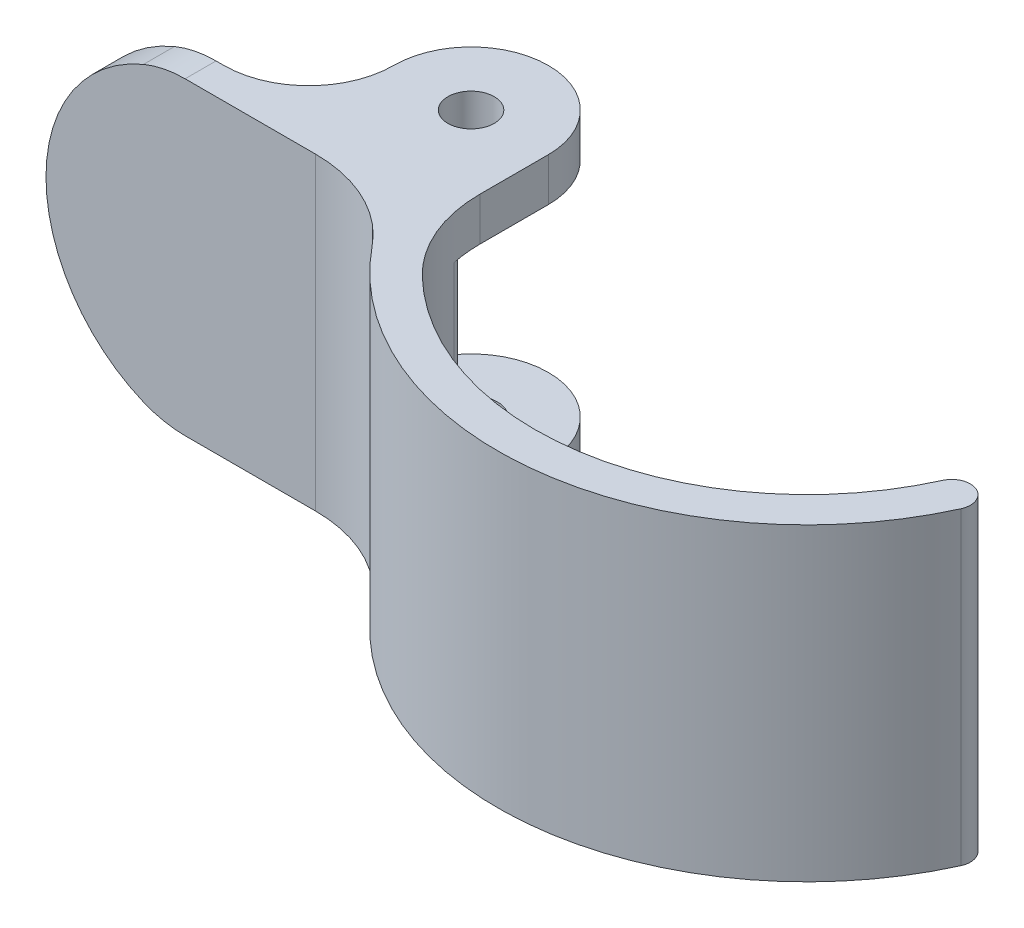
SolidWorks part; units mm, degrees
ref_plane "Front Plane" through (0, 0, 0) normal (0, 0, 1) x (1, 0, 0)
ref_plane "Top Plane" through (0, 0, 0) normal (0, 1, 0) x (1, 0, 0)
ref_plane "Right Plane" through (0, 0, 0) normal (1, 0, 0) x (0, 0, -1)
sketch "Sketch1" plane through (0, 0, 0) normal (0, 0, 1) x (1, 0, 0)
  line L0 (0, 10) -> (0, -10) construction
  line L1 (-12, -10) -> (5, -10)
  line L2 (-12, -10) -> (-12, 10)
  line L3 (-12, 10) -> (5, 10)
  line L4 (5, -10) -> (5, 10)
  dimension "D1" = 20
  dimension "D2" = 12
  dimension "D3" = 5
extrude "Boss-Extrude1" add sketch "Sketch1" along normal blind 2
sketch "Sketch2" plane through (0, 10, 0) normal (0, 1, 0) x (1, 0, 0)
  line L0 (0, 0) -> (0, 5.5) construction
  line L1 (5, 0) -> (-5, 0)
  line L2 (5, 0) -> (-12, 0) construction
  line L3 (-5, 0) -> (-5, 5.5)
  line L4 (5, 0) -> (5, 5.5)
  line L5 (-5, 5.5) -> (5, 5.5) construction
  circle A0 centre (0, 5.5) radius 1.5
  arc A1 (-5, 5.5) -> (5, 5.5) centre (0, 5.5) cw
  dimension "D1" = 3
  dimension "D2" = 5
  dimension "D3" = 5.5
extrude "Boss-Extrude2" add sketch "Sketch2" against normal blind 2.8
fillet "Fillet1" radius 5.5 1 edges at (-5, 8.6, 0)
mirror "Mirror1" about plane through (0, 0, 0) normal (0, 1, 0) of "Fillet1", "Boss-Extrude2"
hole_wizard "CSK for M3 Countersunk Flat Head Screw1" positions "Sketch3" profile "Sketch4" countersink size "M3" standard "DIN"
sketch "Sketch3" plane through (0, -10, 0) normal (0, -1, 0) x (-1, 0, 0)
  point P0 (0, 5.5)
sketch "Sketch4" plane through (0, -10, -5.5) normal (1, 0, 0) x (0, 0, -1)
  line L0 (0, 0) -> (0, 8.0215)
  line L1 (0, 8.0215) -> (1.7, 7)
  line L2 (1.7, 7) -> (1.7, 1.45)
  line L3 (1.7, 1.45) -> (3.15, 0)
  line L5 (3.15, 0) -> (0, 0)
  line L6 (-1.7, 1.45) -> (-3.15, 0) construction
  line L10 (0, 8.0215) -> (-1.7, 7) construction
  line L11 (0, -6.35) -> (0, 107.95) construction
  dimension "Hole Dia." = 3.4
  dimension "Hole Depth" = 7
  dimension "Near C'Sink Dia." = 6.3
  dimension "Near C'Sink Angle" = 90
  dimension "Drill Angle" = 118
sketch "Sketch5" plane through (0, 0, 2) normal (0, 0, 1) x (1, 0, 0)
  line L0 (0, 0) -> (-20, 0) construction
  line L1 (-12, 10) -> (-12, -10)
  line L2 (5, 10) -> (-12, 10) construction
  line L3 (-12, -10) -> (5, -10) construction
  line L4 (-12, 10) -> (-12, -10) construction
  arc A0 (-12, -10) -> (-12, 10) centre (-9.75, 0) cw
  dimension "D1" = 20
extrude "Boss-Extrude3" add sketch "Sketch5" against normal up to surface (2 mm away) up to face at (-7, 0, 0)
fillet "Fillet2" radius 7 2 edges at (-12, -10, 1) (-12, 10, 1)
sketch "Sketch6" plane through (0, 10, 0) normal (0, 1, 0) x (1, 0, 0)
  line L0 (0, 0) -> (36, 0) construction
  line L2 (2.2399, -2) -> (4.3672, -0.8888)
  line L3 (5, -2) -> (-11, -2) construction
  arc A0 (4.3672, -0.8888) -> (17.5794, -10.1774) centre (19.9671, 7.2599) ccw construction
  arc A1 (2.2399, -2) -> (38.1863, -0.99) centre (19.9671, 7.2599) ccw
  arc A2 (4.3672, -0.8888) -> (36, 0) centre (19.9671, 7.2599) ccw
  arc A3 (2.2399, -2) -> (17.2538, -12.5552) centre (19.9671, 7.2599) ccw construction
  arc A4 (36, 0) -> (38.1863, -0.99) centre (37.0932, -0.495) cw
  dimension "D2" = 2.4
  dimension "D3" = 20
  dimension "D4" = 36
extrude "Boss-Extrude4" add sketch "Sketch6" against normal up to surface (20 mm away) up to face at (0, -10, -8.65)
fillet "Fillet3" radius 9 1 edges at (5, 0, 2)
fillet "Fillet4" radius 9 1 edges at (2.2399, 0, 2)
fillet "Fillet5" radius 1 1 edges at (5.0635, 0, 0)
